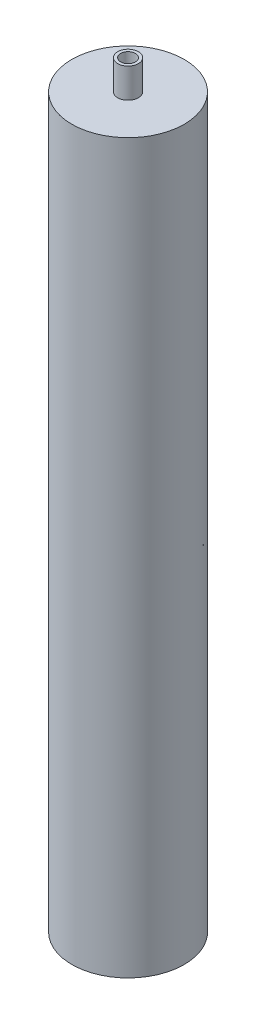
SolidWorks part; units mm, degrees
material "ABS"
ref_plane "前视基准面" through (0, 0, 0) normal (0, 0, 1) x (1, 0, 0)
ref_plane "上视基准面" through (0, 0, 0) normal (0, 1, 0) x (1, 0, 0)
ref_plane "右视基准面" through (0, 0, 0) normal (1, 0, 0) x (0, 0, -1)
sketch "草图1" plane through (0, 0, 0) normal (0, 1, 0) x (1, 0, 0)
  circle A0 centre (0, 0) radius 19
  circle A1 centre (0, 0) radius 18
  dimension "D1" = 38
  dimension "D2" = 36
extrude "凸台-拉伸1" add sketch "草图1" along normal blind 200
sketch "草图2" plane through (0, 200, 0) normal (0, 1, 0) x (1, 0, 0)
  line L10 (-11.485, 0) -> (-15.61, 0)
  line L11 (-15.61, 0) -> (-15.61, 6.2)
  line L12 (-15.61, 6.2) -> (-11.485, 6.2)
  line L13 (-11.485, 6.2) -> (-11.485, 0)
  circle A0 centre (0, 0) radius 19
  circle A2 centre (0, 0) radius 10 construction
  circle A3 centre (0, 10) radius 2 construction
  circle A4 centre (10, 0) radius 2 construction
  circle A5 centre (-10, 0) radius 2 construction
  circle A6 centre (0, -10) radius 2 construction
  circle A7 centre (0, 0) radius 2.5
  dimension "D1" = 38
  dimension "D2" = 20
  dimension "D3" = 4
  dimension "D4" = 4
  dimension "D5" = 4
  dimension "D6" = 4
  dimension "D7" = 5
  dimension "D11" = 5.61
  dimension "D12" = 6.2
  dimension "D13" = 4.125
extrude "凸台-拉伸2" add sketch "草图2" along normal blind 2
sketch "草图3" plane through (0, 202, 0) normal (0, 1, 0) x (1, 0, 0)
  circle A0 centre (0, 0) radius 19
  circle A1 centre (0, 0) radius 18
  dimension "D1" = 38
  dimension "D2" = 36
extrude "凸台-拉伸3" add sketch "草图3" along normal blind 40
sketch "草图4" plane through (0, 242, 0) normal (0, 1, 0) x (1, 0, 0)
  circle A0 centre (0, 0) radius 19
  circle A1 centre (0, 0) radius 2.5
  dimension "D1" = 38
  dimension "D2" = 5
extrude "凸台-拉伸4" add sketch "草图4" along normal blind 2
sketch "草图5" plane through (0, 244, 0) normal (0, 1, 0) x (1, 0, 0)
  circle A0 centre (0, 0) radius 2.5
  circle A1 centre (0, 0) radius 3.5
  dimension "D1" = 5
  dimension "D2" = 7
extrude "凸台-拉伸5" add sketch "草图5" along normal blind 10
sketch "草图6" plane through (0, 0, 0) normal (0, -1, 0) x (1, 0, 0)
  circle A0 centre (0, 0) radius 19
  circle A1 centre (0, 0) radius 12.5
  dimension "D1" = 38
  dimension "D2" = 25
extrude "凸台-拉伸6" add sketch "草图6" along normal blind 2
sketch "草图7" plane through (0, 0, 0) normal (0, 0, 1) x (1, 0, 0)
  line L0 (0, 200) -> (0, 154.22) construction
  line L1 (-18, 200) -> (18, 200) construction
  circle A0 centre (0, 154.22) radius 1.5
  dimension "D2" = 3
  dimension "D1" = 45.78
extrude "凸台-拉伸7" add sketch "草图7" against normal up to next and the other way up to next
ref_plane "基准面1" through (0, 139, 0) normal (0, -1, 0) x (-1, 0, 0)
sketch "草图8" plane through (0, 139, 0) normal (0, -1, 0) x (-1, 0, 0)
  line L3 (0, 0) -> (-18, 0)
  line L4 (0, 0) -> (0, -5)
  line L5 (0, -5) -> (-17.2916, -5)
  arc A3 (-18, 0) -> (-17.2916, -5) centre (0, 0) ccw
  dimension "D2" = 36
  dimension "D3" = 5
extrude "凸台-拉伸9" add sketch "草图8" along normal blind 3
ref_plane "基准面2" through (0, 88, 0) normal (0, -1, 0) x (-1, 0, 0)
sketch "草图9" plane through (0, 88, 0) normal (0, -1, 0) x (-1, 0, 0)
  circle A0 centre (0, 0) radius 18
  circle A1 centre (0, 0) radius 2.5
  dimension "D1" = 36
  dimension "D2" = 5
extrude "凸台-拉伸10" add sketch "草图9" along normal blind 2
